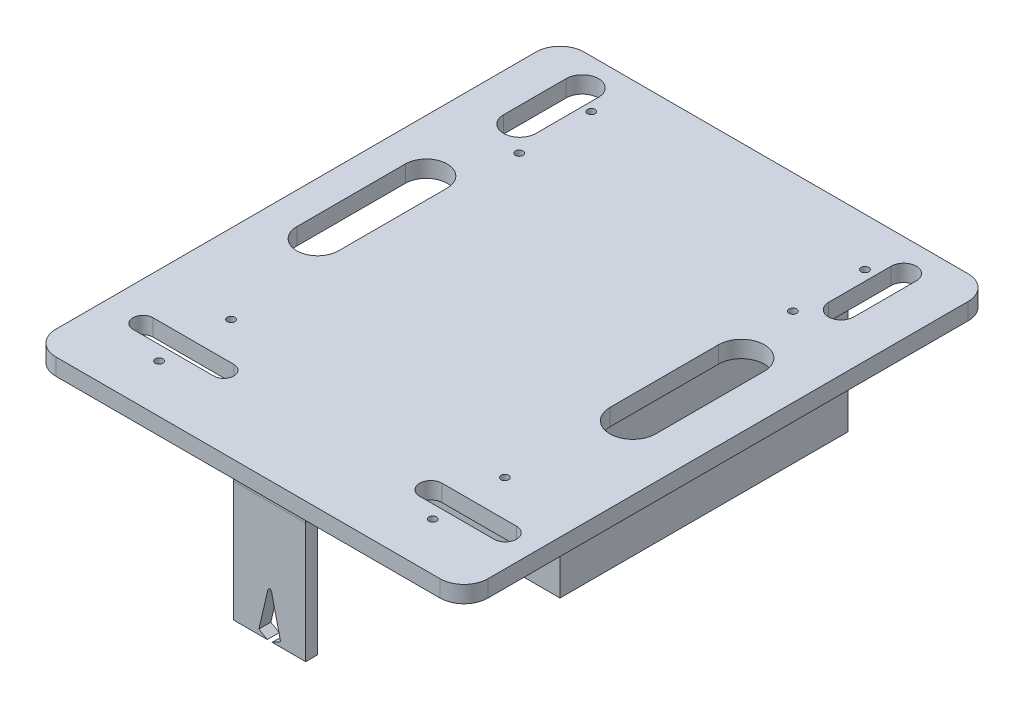
SolidWorks part; units mm, degrees
ref_plane "前视基准面" through (0, 0, 0) normal (0, 0, 1) x (1, 0, 0)
ref_plane "上视基准面" through (0, 0, 0) normal (0, 1, 0) x (1, 0, 0)
ref_plane "右视基准面" through (0, 0, 0) normal (1, 0, 0) x (0, 0, -1)
sketch "草图1" plane through (0, 0, 0) normal (0, 1, 0) x (1, 0, 0)
  line L0 (-95.2597, 129.0909) -> (-62.2597, 129.0909) construction
  line L1 (-85.2597, 139.0909) -> (74.7403, 139.0909)
  line L2 (-95.2597, 129.0909) -> (-95.2597, -70.9091)
  line L3 (-85.2597, -80.9091) -> (74.7403, -80.9091)
  line L4 (84.7403, 129.0909) -> (84.7403, -70.9091)
  line L5 (-62.2597, 139.0909) -> (-62.2597, 89.0909) construction
  line L6 (84.7403, 129.0909) -> (51.7403, 129.0909) construction
  line L7 (51.7403, 139.0909) -> (51.7403, 89.0909) construction
  line L8 (-95.2597, -70.9091) -> (-62.2597, -70.9091) construction
  line L9 (-62.2597, -80.9091) -> (-62.2597, -30.9091) construction
  line L10 (84.7403, -70.9091) -> (51.7403, -70.9091) construction
  line L11 (51.7403, -70.9091) -> (51.7403, -80.9091) construction
  line L12 (51.7403, -80.9091) -> (51.7403, -30.9091) construction
  arc A0 (-85.2597, 139.0909) -> (-95.2597, 129.0909) centre (-85.2597, 129.0909) ccw
  arc A1 (74.7403, 139.0909) -> (84.7403, 129.0909) centre (74.7403, 129.0909) cw
  arc A2 (74.7403, -80.9091) -> (84.7403, -70.9091) centre (74.7403, -70.9091) ccw
  arc A3 (-95.2597, -70.9091) -> (-85.2597, -80.9091) centre (-85.2597, -70.9091) ccw
  circle A4 centre (-62.2597, 89.0909) radius 1.6
  circle A5 centre (51.7403, 89.0909) radius 1.6
  circle A6 centre (-62.2597, -30.9091) radius 1.6
  circle A7 centre (51.7403, -30.9091) radius 1.6
  point P6 (-95.2597, 139.0909)
  point P9 (84.7403, 139.0909)
  point P14 (-95.2597, -80.9091)
  dimension "D3" = 10
  dimension "D4" = 10
  dimension "D5" = 10
  dimension "D6" = 10
  dimension "D1" = 180
  dimension "D2" = 220
extrude "凸台-拉伸1" add sketch "草图1" along normal blind 7
sketch "草图2" plane through (0, 0, 0) normal (0, -1, 0) x (1, 0, 0)
  line L0 (-5.2597, 80.9091) -> (-5.2597, -139.0909) construction
  line L1 (-85.2597, 80.9091) -> (74.7403, 80.9091) construction
  line L2 (74.7403, -139.0909) -> (-85.2597, -139.0909) construction
  line L3 (-95.2597, -29.0909) -> (84.7403, -29.0909) construction
  line L4 (-95.2597, -129.0909) -> (-95.2597, 70.9091) construction
  line L5 (84.7403, 70.9091) -> (84.7403, -129.0909) construction
  line L6 (-5.2597, -29.0909) -> (-45.2597, -29.0909) construction
  line L7 (-5.2597, -29.0909) -> (34.7403, -29.0909) construction
  line L8 (-45.2597, -29.0909) -> (-45.2597, -119.0909) construction
  line L9 (-45.2597, -119.0909) -> (34.7403, -119.0909) construction
  line L10 (34.7403, -119.0909) -> (34.7403, -29.0909) construction
  line L11 (34.7403, -29.0909) -> (-45.2597, -29.0909) construction
  line L12 (-45.2597, -29.0909) -> (-45.2597, -9.0909) construction
  line L13 (-45.2597, -9.0909) -> (34.7403, -9.0909) construction
  line L14 (34.7403, -9.0909) -> (34.7403, -29.0909) construction
  line L15 (-45.2597, -9.0909) -> (-50.2597, -9.0909) construction
  line L16 (34.7403, -9.0909) -> (-45.2597, -9.0909)
  line L17 (34.7403, -9.0909) -> (34.7403, -119.0909)
  line L18 (34.7403, -119.0909) -> (-45.2597, -119.0909)
  line L19 (-45.2597, -9.0909) -> (-45.2597, -119.0909)
  line L20 (-45.2597, -9.0909) -> (-45.2597, -4.0909) construction
  line L21 (34.7403, -119.0909) -> (34.7403, -124.0909) construction
  line L22 (34.7403, -119.0909) -> (39.7403, -119.0909) construction
  line L24 (39.7403, -124.0909) -> (-50.2597, -124.0909)
  line L25 (39.7403, -124.0909) -> (39.7403, -4.0909)
  line L26 (39.7403, -4.0909) -> (-50.2597, -4.0909)
  line L27 (-50.2597, -124.0909) -> (-50.2597, -4.0909)
extrude "凸台-拉伸2" add sketch "草图2" along normal blind 60
sketch "草图3" plane through (0, 0, 0) normal (0, -1, 0) x (1, 0, 0)
  line L0 (-5.2597, 80.9091) -> (-5.2597, 7.1374) construction
  line L1 (-85.2597, 80.9091) -> (74.7403, 80.9091) construction
  line L2 (-5.2597, 7.1374) -> (-30.2597, 7.1374) construction
  line L3 (-5.2597, 7.1374) -> (19.7403, 7.1374) construction
  line L4 (-30.2597, 7.1374) -> (-30.2597, 37.1374) construction
  line L5 (-30.2597, 37.1374) -> (19.7403, 37.1374) construction
  line L6 (19.7403, 37.1374) -> (19.7403, 7.1374) construction
  line L7 (-30.2597, 37.1374) -> (-33.2597, 37.1374) construction
  line L8 (-30.2597, 7.1374) -> (19.7403, 7.1374)
  line L9 (-30.2597, 7.1374) -> (-30.2597, 37.1374)
  line L10 (-30.2597, 37.1374) -> (19.7403, 37.1374)
  line L11 (19.7403, 7.1374) -> (19.7403, 37.1374)
  line L12 (-30.2597, 37.1374) -> (-30.2597, 40.1374) construction
  line L13 (19.7403, 7.1374) -> (19.7403, 4.1374) construction
  line L14 (19.7403, 7.1374) -> (22.7403, 7.1374) construction
  line L16 (-33.2597, 40.1374) -> (22.7403, 40.1374)
  line L17 (-33.2597, 40.1374) -> (-33.2597, 4.1374)
  line L18 (-33.2597, 4.1374) -> (22.7403, 4.1374)
  line L19 (22.7403, 40.1374) -> (22.7403, 4.1374)
extrude "凸台-拉伸3" add sketch "草图3" along normal blind 10
sketch "草图5" plane through (0, -10, 0) normal (0, -1, 0) x (1, 0, 0)
  line L0 (-33.2597, 4.1374) -> (-33.2597, 7.1374)
  line L1 (-33.2597, 40.1374) -> (-33.2597, 4.1374) construction
  line L2 (-33.2597, 7.1374) -> (22.7403, 7.1374)
  line L3 (22.7403, 4.1374) -> (22.7403, 40.1374) construction
  line L4 (22.7403, 7.1374) -> (22.7403, 4.1374)
  line L5 (22.7403, 4.1374) -> (-33.2597, 4.1374)
extrude "凸台-拉伸4" add sketch "草图5" along normal blind 20
sketch "草图6" plane through (0, 0, 0) normal (0, -1, 0) x (1, 0, 0)
  line L0 (-5.2597, 80.9091) -> (-5.2597, 71.8328) construction
  line L1 (-85.2597, 80.9091) -> (74.7403, 80.9091) construction
  line L2 (-5.2597, 71.8328) -> (-5.2597, 66.8328) construction
  line L3 (-5.2597, 66.8328) -> (9.7403, 66.8328) construction
  line L4 (-5.2597, 66.8328) -> (-20.2597, 66.8328) construction
  line L5 (-20.2597, 66.8328) -> (-20.2597, 71.8328) construction
  line L6 (-20.2597, 71.8328) -> (9.7403, 71.8328) construction
  line L8 (9.7403, 71.8328) -> (-20.2597, 71.8328)
  line L9 (9.7403, 71.8328) -> (9.7403, 66.8328)
  line L10 (9.7403, 66.8328) -> (-20.2597, 66.8328)
  line L11 (-20.2597, 71.8328) -> (-20.2597, 66.8328)
extrude "凸台-拉伸5" add sketch "草图6" along normal blind 60
sketch "草图8" plane through (0, 0, 71.8328) normal (0, 0, 1) x (1, 0, 0)
  line L0 (9.7403, -60) -> (-3.7597, -60) construction
  line L1 (9.7403, -60) -> (-20.2597, -60) construction
  line L2 (-20.2597, -60) -> (-6.7597, -60) construction
  line L3 (-5.2597, 0) -> (-5.2597, -60) construction
  line L4 (9.7403, 0) -> (-20.2597, 0) construction
  line L5 (-5.2597, -60) -> (-5.2597, -41) construction
  line L6 (-5.2597, -60) -> (-10.2597, -60) construction
  line L7 (-5.2597, -60) -> (-0.2597, -60) construction
  line L8 (-5.2597, -41) -> (-6.2597, -41) construction
  line L9 (-5.2597, -41) -> (-4.2597, -41) construction
  line L10 (-5.2597, -41) -> (-5.2597, -43) construction
  line L11 (-5.2597, -43) -> (-6.2597, -43) construction
  line L12 (-6.2597, -43) -> (-5.2597, -43) construction
  line L13 (-5.2597, -43) -> (-4.2597, -43) construction
  line L14 (-6.2597, -43) -> (-10.2597, -60)
  line L15 (-4.2597, -43) -> (-0.2597, -60)
  line L16 (-10.2597, -60) -> (-0.2597, -60)
  arc A0 (-6.2597, -43) -> (-5.2597, -41) centre (-3.7597, -43) cw
  arc A1 (-4.2597, -43) -> (-5.2597, -41) centre (-6.7597, -43) ccw
  dimension "D1" = 2
extrude "切除-拉伸1" cut sketch "草图8" against normal blind 10
sketch "草图9" plane through (0, 0, 71.8328) normal (0, 0, 1) x (1, 0, 0)
  line L0 (-10.2597, -60) -> (-6.2597, -60) construction
  line L1 (39.7403, -60) -> (-50.2597, -60) construction
  line L2 (-0.2597, -60) -> (-4.2597, -60) construction
  line L3 (-6.2597, -60) -> (-6.2597, -58) construction
  line L4 (-4.2597, -60) -> (-4.2597, -58) construction
  line L5 (-6.2597, -60) -> (-9.7892, -58)
  line L6 (-6.2597, -43) -> (-10.2597, -60) construction
  line L7 (-9.7892, -58) -> (-10.2597, -60)
  line L8 (-10.2597, -60) -> (-6.2597, -60)
  line L9 (-4.2597, -60) -> (-0.2597, -60)
  line L10 (-4.2597, -60) -> (-0.7303, -58)
  line L11 (-0.2597, -60) -> (-4.2597, -43) construction
  line L12 (-0.7303, -58) -> (-0.2597, -60)
extrude "凸台-拉伸6" add sketch "草图9" against normal blind 5
sketch "草图10" plane through (0, 0, 0) normal (0, -1, 0) x (1, 0, 0)
  line L0 (-73.3698, -16.2598) -> (-73.3698, -61.4888) construction
  line L1 (-64.659, -16.2598) -> (-64.659, -61.4888)
  line L2 (-82.0806, -16.2598) -> (-82.0806, -61.4888)
  line L3 (57.9069, -16.2598) -> (57.9069, -61.4888) construction
  line L4 (67.4592, -16.2598) -> (67.4592, -61.4888)
  line L5 (48.3545, -16.2598) -> (48.3545, -61.4888)
  arc A0 (-64.659, -16.2598) -> (-82.0806, -16.2598) centre (-73.3698, -16.2598) ccw
  arc A1 (-82.0806, -61.4888) -> (-64.659, -61.4888) centre (-73.3698, -61.4888) ccw
  arc A2 (67.4592, -16.2598) -> (48.3545, -16.2598) centre (57.9069, -16.2598) ccw
  arc A3 (48.3545, -61.4888) -> (67.4592, -61.4888) centre (57.9069, -61.4888) ccw
  point P2 (-73.3698, -38.8743)
  point P9 (57.9069, -38.8743)
extrude "切除-拉伸2" cut sketch "草图10" against normal blind 10
sketch "草图12" plane through (0, 0, 0) normal (0, -1, 0) x (1, 0, 0)
  line L0 (-72.6422, -99.696) -> (-72.6422, -125.7701) construction
  line L1 (-65.9039, -99.696) -> (-65.9039, -125.7701)
  line L2 (-79.3804, -99.696) -> (-79.3804, -125.7701)
  line L3 (61.2438, -99.696) -> (61.2438, -125.7701) construction
  line L4 (66.5172, -99.696) -> (66.5172, -125.7701)
  line L5 (55.9704, -99.696) -> (55.9704, -125.7701)
  arc A0 (-65.9039, -99.696) -> (-79.3804, -99.696) centre (-72.6422, -99.696) ccw
  arc A1 (-79.3804, -125.7701) -> (-65.9039, -125.7701) centre (-72.6422, -125.7701) ccw
  arc A2 (66.5172, -99.696) -> (55.9704, -99.696) centre (61.2438, -99.696) ccw
  arc A3 (55.9704, -125.7701) -> (66.5172, -125.7701) centre (61.2438, -125.7701) ccw
  point P2 (-72.6422, -112.733)
  point P7 (61.2438, -112.733)
extrude "切除-拉伸4" cut sketch "草图12" against normal blind 10
sketch "草图13" plane through (0, 7, 0) normal (0, 1, 0) x (1, 0, 0)
  line L0 (-95.2597, 129.0909) -> (-62.2597, 129.0909) construction
  line L1 (-62.2597, 139.0909) -> (-62.2597, 119.0909) construction
  line L2 (74.7403, 139.0909) -> (-85.2597, 139.0909) construction
  line L3 (84.7403, 129.0909) -> (51.7403, 129.0909) construction
  line L4 (51.7403, 139.0909) -> (51.7403, 119.0909) construction
  line L5 (-95.2597, -70.9091) -> (-62.2597, -70.9091) construction
  line L6 (-62.2597, -80.9091) -> (-62.2597, -60.9091) construction
  line L7 (-85.2597, -80.9091) -> (74.7403, -80.9091) construction
  line L8 (74.7403, -80.9091) -> (74.7403, -60.9091) construction
  line L9 (84.7403, -60.9091) -> (51.7403, -60.9091) construction
  line L10 (84.7403, -70.9091) -> (84.7403, 129.0909) construction
  circle A0 centre (-62.2597, 119.0909) radius 1.6
  circle A1 centre (51.7403, 119.0909) radius 1.6
  circle A2 centre (-62.2597, -60.9091) radius 1.6
  circle A3 centre (51.7403, -60.9091) radius 1.6
  dimension "D1" = 33
extrude "切除-拉伸5" cut sketch "草图13" against normal blind 10
sketch "草图14" plane through (0, 0, 0) normal (0, -1, 0) x (-1, 0, 0)
  line L0 (79.1701, -50.7267) -> (45.4996, -50.7267) construction
  line L1 (79.1701, -54.9146) -> (45.4996, -54.9146)
  line L2 (79.1701, -46.5389) -> (45.4996, -46.5389)
  line L3 (-40.7705, -50.7267) -> (-71.7608, -50.7267) construction
  line L4 (-40.7705, -55.4171) -> (-71.7608, -55.4171)
  line L5 (-40.7705, -46.0363) -> (-71.7608, -46.0363)
  arc A0 (79.1701, -54.9146) -> (79.1701, -46.5389) centre (79.1701, -50.7267) ccw
  arc A1 (45.4996, -46.5389) -> (45.4996, -54.9146) centre (45.4996, -50.7267) ccw
  arc A2 (-40.7705, -55.4171) -> (-40.7705, -46.0363) centre (-40.7705, -50.7267) ccw
  arc A3 (-71.7608, -46.0363) -> (-71.7608, -55.4171) centre (-71.7608, -50.7267) ccw
  point P2 (62.3348, -50.7267)
  point P7 (-56.2656, -50.7267)
extrude "切除-拉伸6" cut sketch "草图14" against normal blind 10
sketch "草图16" plane through (0, 0, -124.0909) normal (0, 0, -1) x (-1, 0, 0)
  line L0 (6.2597, -60) -> (6.2597, -50) construction
  line L1 (50.2597, -60) -> (50.2597, -55) construction
  line L2 (50.2597, -60) -> (50.2597, 0) construction
  line L3 (50.2597, -55) -> (40.2597, -55) construction
  line L4 (-39.7403, -55) -> (-29.7403, -55) construction
  line L5 (-39.7403, -60) -> (-39.7403, 0) construction
  line L7 (-29.7403, -55) -> (40.2597, -55)
  line L8 (-29.7403, -55) -> (-29.7403, -50)
  line L9 (-29.7403, -50) -> (40.2597, -50)
  line L10 (40.2597, -55) -> (40.2597, -50)
extrude "切除-拉伸7" cut sketch "草图16" against normal blind 10
fillet "圆角1" radius 10 1 edges at (-5.2597, 0, 71.8328)
fillet "圆角2" radius 10 1 edges at (-5.2597, 0, 66.8328)
fillet "圆角3" radius 10 1 edges at (-20.2597, 0, 68.8709)
fillet "圆角4" radius 10 1 edges at (9.7403, 0, 68.8709)
